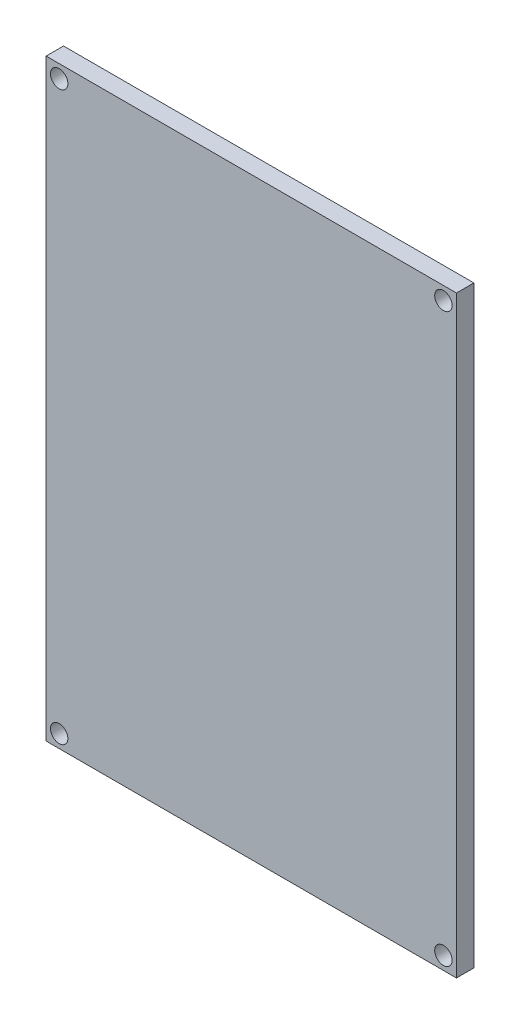
SolidWorks part; units mm, degrees
material "ABS"
ref_plane "Front Plane" through (0, 0, 0) normal (0, 0, 1) x (1, 0, 0)
ref_plane "Top Plane" through (0, 0, 0) normal (0, 1, 0) x (1, 0, 0)
ref_plane "Right Plane" through (0, 0, 0) normal (1, 0, 0) x (0, 0, -1)
sketch "Sketch1" plane through (0, 0, 0) normal (0, 0, 1) x (1, 0, 0)
  line L0 (66.841, 51.091) -> (70.682, 51.091) construction
  line L1 (3.841, 51.091) -> (0, 51.091) construction
  line L2 (35.341, 3.841) -> (35.341, 0) construction
  line L3 (35.341, 98.341) -> (35.341, 102.182) construction
  line L5 (0, 0) -> (70.682, 0)
  line L6 (0, 0) -> (0, 102.182)
  line L7 (0, 102.182) -> (70.682, 102.182)
  line L8 (70.682, 0) -> (70.682, 102.182)
  line L14 (0, 0) -> (1.1893, 1.1893) construction
  line L16 (3.3107, 3.3107) -> (1.1893, 1.1893) construction
  line L17 (0.75, 2.25) -> (0, 2.25) construction
  line L18 (3.841, 3.841) -> (66.841, 3.841)
  line L19 (3.841, 3.841) -> (3.841, 98.341)
  line L20 (3.841, 98.341) -> (66.841, 98.341)
  line L21 (66.841, 3.841) -> (66.841, 98.341)
  line L25 (3.3107, 3.3107) -> (3.841, 3.841)
  circle A0 centre (68.432, 2.25) radius 1.5
  circle A1 centre (2.25, 99.932) radius 1.5
  circle A2 centre (68.432, 99.932) radius 1.5
  circle A3 centre (22, 72) radius 2.2361
  circle A4 centre (35, 21) radius 2.2361
  circle A5 centre (2.25, 2.25) radius 1.5
  circle A6 centre (50, 73) radius 1.4142
  dimension "D17" = 3
  dimension "D2" = 63
  dimension "D3" = 94.5
  dimension "D18" = 0.75
extrude "Boss-Extrude2" add sketch "Sketch1" along normal blind 3 contours L18 L21 L20 L19 A6 A4 A3 | L5 L8 L7 L6 A2 A0 A5 L19 L20 L21 L18 A1 | A3 | A6 | A4 region at (1.2425, 51.091, 0) region at (35.3618, 51.0921, 0) region at (22, 72, 0) region at (35, 21, 0) region at (50, 73, 0)
extrude "Boss-Extrude3" add sketch "Sketch1<27>" against normal blind 14.35 contours A4 | A6 | A3 region at (22, 72, 0) region at (35, 21, 0) region at (50, 73, 0)
sketch "Sketch1<27>" plane through (0, 0, 0) normal (0, 0, 1) x (1, 0, 0) same geometry as "Sketch1"
